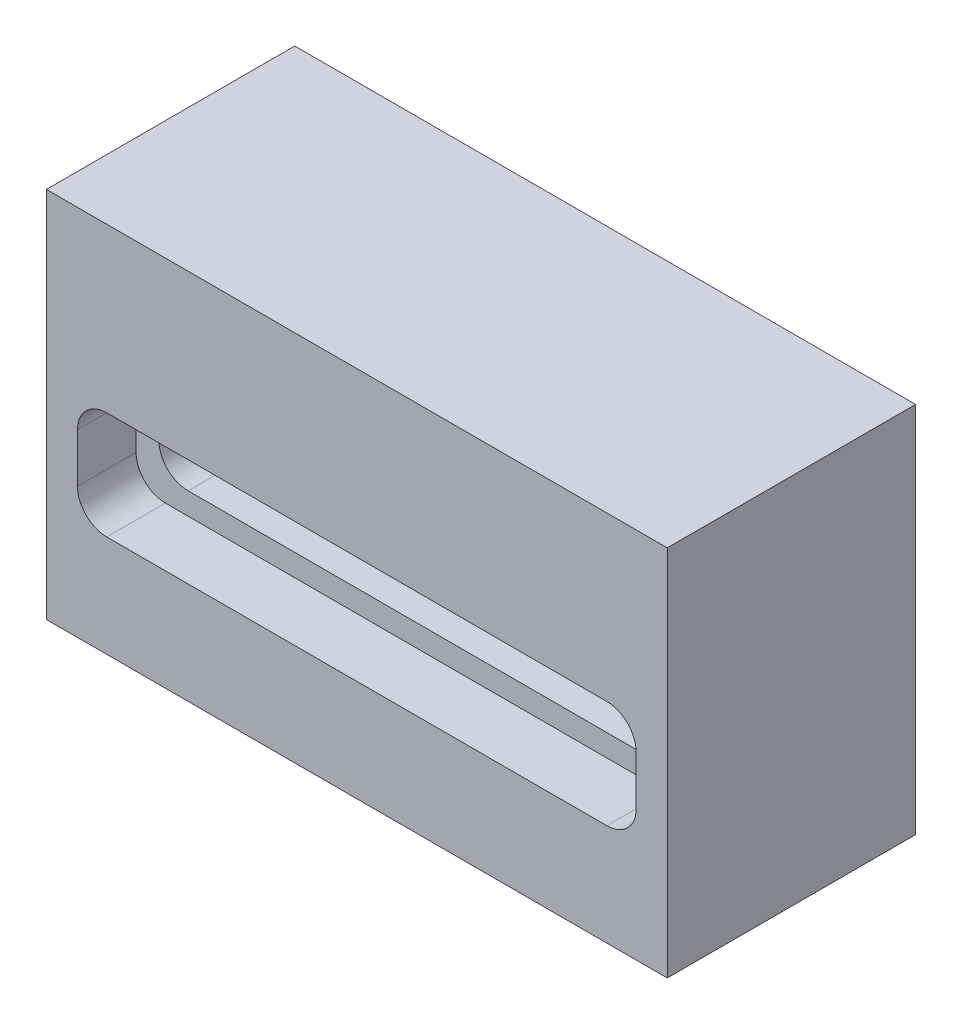
SolidWorks part; units mm, degrees
ref_plane "Front Plane" through (0, 0, 0) normal (0, 0, 1) x (1, 0, 0)
ref_plane "Top Plane" through (0, 0, 0) normal (0, 1, 0) x (1, 0, 0)
ref_plane "Right Plane" through (0, 0, 0) normal (1, 0, 0) x (0, 0, -1)
sketch "Sketch1" plane through (0, 0, 0) normal (0, 1, 0) x (1, 0, 0)
  line L1 (0, 0) -> (127, 0)
  line L2 (0, 0) -> (0, 50.8)
  line L3 (0, 50.8) -> (127, 50.8)
  line L4 (127, 0) -> (127, 50.8)
  dimension "D1" = 50.8
  dimension "D2" = 127
extrude "Boss-Extrude1" add sketch "Sketch1" along normal blind 76.2
sketch "Sketch2" plane through (0, 0, 0) normal (0, 0, 1) x (1, 0, 0)
  line L1 (0, 0) -> (63.5, 0)
  line L2 (0, 0) -> (0, 31.8)
  line L3 (0, 31.8) -> (63.5, 31.8)
  line L4 (63.5, 0) -> (63.5, 31.8)
  line L5 (17, 38.3) -> (110, 38.3)
  line L6 (11, 32.3) -> (11, 31.3)
  line L7 (17, 25.3) -> (110, 25.3)
  line L8 (116, 32.3) -> (116, 31.3)
  line L9 (11, 38.3) -> (116, 25.3) construction
  line L10 (11, 25.3) -> (116, 38.3) construction
  arc A0 (110, 38.3) -> (116, 32.3) centre (110, 32.3) cw
  arc A1 (110, 25.3) -> (116, 31.3) centre (110, 31.3) ccw
  arc A2 (11, 31.3) -> (17, 25.3) centre (17, 31.3) ccw
  arc A3 (17, 38.3) -> (11, 32.3) centre (17, 32.3) ccw
  dimension "D5" = 6
  dimension "D1" = 31.8
  dimension "D2" = 63.5
  dimension "D3" = 105
  dimension "D4" = 13
sketch "Sketch3" plane through (0, 0, 0) normal (0, 0, 1) x (1, 0, 0)
  line L1 (0, 0) -> (63.5, 0)
  line L2 (0, 0) -> (0, 31.8)
  line L3 (0, 31.8) -> (63.5, 31.8)
  line L4 (63.5, 0) -> (63.5, 31.8)
  line L5 (12.35, 42.8) -> (114.65, 42.8)
  line L6 (6.35, 36.8) -> (6.35, 26.8)
  line L7 (12.35, 20.8) -> (114.65, 20.8)
  line L8 (120.65, 36.8) -> (120.65, 26.8)
  line L9 (6.35, 42.8) -> (120.65, 20.8) construction
  line L10 (6.35, 20.8) -> (120.65, 42.8) construction
  arc A0 (12.35, 42.8) -> (6.35, 36.8) centre (12.35, 36.8) ccw
  arc A1 (6.35, 26.8) -> (12.35, 20.8) centre (12.35, 26.8) ccw
  arc A2 (114.65, 20.8) -> (120.65, 26.8) centre (114.65, 26.8) ccw
  arc A3 (114.65, 42.8) -> (120.65, 36.8) centre (114.65, 36.8) cw
  dimension "D4" = 6
  dimension "D1" = 63.5
  dimension "D2" = 31.8
  dimension "D3" = 114.3
  dimension "D5" = 10
extrude "Cut-Extrude2" cut sketch "Sketch3" against normal blind 12 contours L5 A3 L8 A2 L7 A1 L6 A0
extrude "Cut-Extrude3" cut sketch "Sketch2" against normal through all contours L5 A0 L8 A1 L7 A2 L6 A3
